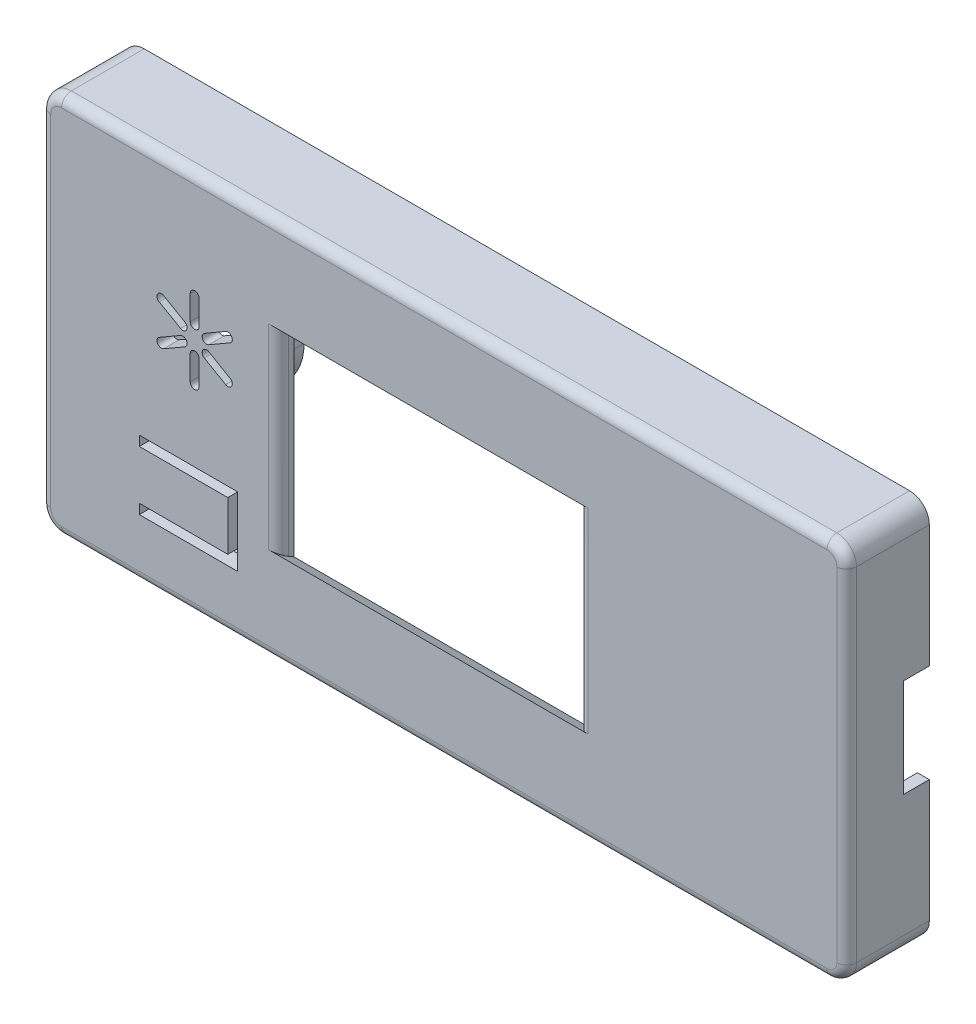
SolidWorks part; units mm, degrees
note: The reader was unsure of these and kept them because the rebuilt part matched: shared geometry of "Skizze1<10>", "Skizze1<23>", "Skizze1<24>", "Skizze1<36>", "Skizze1<38>".
ref_plane "Ebene vorne" through (0, 0, 0) normal (0, 0, 1) x (1, 0, 0)
ref_plane "Ebene oben" through (0, 0, 0) normal (0, 1, 0) x (1, 0, 0)
ref_plane "Ebene rechts" through (0, 0, 0) normal (1, 0, 0) x (0, 0, -1)
sketch "Skizze1" plane through (0, 0, 0) normal (0, 0, 1) x (1, 0, 0)
  line L0 (5.9, 21.251) -> (17.6, 21.251)
  line L1 (0, 33) -> (74, 33)
  line L2 (0, 33) -> (0, 0)
  line L3 (0, 0) -> (74, 0)
  line L4 (74, 33) -> (74, 0)
  line L5 (9, 8.7) -> (15, 8.7)
  line L6 (9, 8.7) -> (9, 2.9)
  line L7 (9, 2.9) -> (15, 2.9)
  line L8 (15, 8.7) -> (15, 2.9)
  line L9 (50, 30.1) -> (21, 30.1)
  line L10 (50, 30.1) -> (50, 2.9)
  line L11 (50, 2.9) -> (21, 2.9)
  line L12 (21, 30.1) -> (21, 2.9)
  line L13 (-2, 35) -> (76, 35)
  line L14 (-2, 35) -> (-2, -2)
  line L15 (-2, -2) -> (76, -2)
  line L16 (76, 35) -> (76, -2)
  line L17 (7.4, 21.251) -> (16.1, 21.251)
  line L18 (8.3728, 23.2004) -> (10.5378, 21.9504) construction
  line L19 (8.5978, 23.5901) -> (10.7628, 22.3401)
  line L20 (8.1478, 22.8107) -> (10.3128, 21.5607)
  line L21 (11.3009, 25.1491) -> (11.3009, 22.6491)
  line L22 (70, 21.5) -> (74, 21.5)
  line L23 (70, 21.5) -> (70, 11.5)
  line L24 (70, 11.5) -> (74, 11.5)
  line L25 (74, 21.5) -> (74, 11.5)
  line L26 (21, 30.1) -> (50, 30.1)
  line L27 (21, 30.1) -> (21, 26.1)
  line L28 (21, 26.1) -> (50, 26.1)
  line L29 (50, 30.1) -> (50, 26.1)
  line L30 (12.2009, 25.1491) -> (12.2009, 22.6491)
  line L31 (11.7509, 25.1491) -> (11.7509, 22.6491) construction
  line L32 (14.9026, 23.5875) -> (12.7376, 22.3375)
  line L33 (15.3526, 22.8081) -> (13.1876, 21.5581)
  line L34 (15.1276, 23.1978) -> (12.9626, 21.9478) construction
  line L35 (15.3511, 19.6876) -> (13.1861, 20.9376)
  line L36 (14.9011, 18.9082) -> (12.7361, 20.1582)
  line L37 (15.1261, 19.2979) -> (12.9611, 20.5479) construction
  line L38 (12.198, 17.3492) -> (12.198, 19.8492)
  line L39 (11.298, 17.3492) -> (11.298, 19.8492)
  line L40 (11.748, 17.3492) -> (11.748, 19.8492) construction
  line L41 (8.5963, 18.9108) -> (10.7613, 20.1608)
  line L42 (8.1463, 19.6902) -> (10.3113, 20.9402)
  line L43 (8.3713, 19.3005) -> (10.5363, 20.5505) construction
  arc A1 (5.9, 21.251) -> (17.6, 21.251) centre (11.75, 21.25) cw
  arc A2 (16.1, 21.251) -> (7.4, 21.251) centre (11.75, 21.25) ccw
  arc A3 (8.5978, 23.5901) -> (8.1478, 22.8107) centre (8.3728, 23.2004) ccw
  arc A4 (10.3128, 21.5607) -> (10.7628, 22.3401) centre (10.5378, 21.9504) ccw
  arc A5 (12.2009, 25.1491) -> (11.3009, 25.1491) centre (11.7509, 25.1491) ccw
  arc A6 (11.3009, 22.6491) -> (12.2009, 22.6491) centre (11.7509, 22.6491) ccw
  arc A7 (15.3526, 22.8081) -> (14.9026, 23.5875) centre (15.1276, 23.1978) ccw
  arc A8 (12.7376, 22.3375) -> (13.1876, 21.5581) centre (12.9626, 21.9478) ccw
  arc A9 (14.9011, 18.9082) -> (15.3511, 19.6876) centre (15.1261, 19.2979) ccw
  arc A10 (13.1861, 20.9376) -> (12.7361, 20.1582) centre (12.9611, 20.5479) ccw
  arc A11 (11.298, 17.3492) -> (12.198, 17.3492) centre (11.748, 17.3492) ccw
  arc A12 (12.198, 19.8492) -> (11.298, 19.8492) centre (11.748, 19.8492) ccw
  arc A13 (8.1463, 19.6902) -> (8.5963, 18.9108) centre (8.3713, 19.3005) ccw
  arc A14 (10.7613, 20.1608) -> (10.3113, 20.9402) centre (10.5363, 20.5505) ccw
  arc A15 (16.1, 21.251) -> (7.4, 21.251) centre (11.75, 21.252) cw
  arc A16 (5.9, 21.251) -> (17.6, 21.251) centre (11.75, 21.252) ccw
  point P24 (9.4553, 22.5754)
  point P40 (11.7509, 23.8991)
  point P47 (14.0451, 22.5728)
  point P54 (14.0436, 19.9229)
  point P61 (11.748, 18.5992)
  point P68 (9.4538, 19.9255)
  point P73 (11.7494, 21.2492)
  dimension "D3" = 4.35
  dimension "D16" = 0.45
  dimension "D1" = 33
  dimension "D5" = 11.75
  dimension "D6" = 6
  dimension "D7" = 5.8
  dimension "D8" = 8.7
  dimension "D9" = 15
  dimension "D10" = 74
  dimension "D11" = 2.9
  dimension "D13" = 50
  dimension "D14" = 53
  dimension "D12" = 2.9
  dimension "D15" = 2
  dimension "D17" = 2
  dimension "D18" = 2
  dimension "D19" = 2
  dimension "D20" = 11.7
  dimension "D4" = 2.5
  dimension "D21" = 2.65
  dimension "D22" = 4
  dimension "D23" = 4
  dimension "D24" = 10
  dimension "D25" = 11.5
  dimension "D26" = 4
  dimension "D27" = 11.75
  dimension "D28" = 30
  dimension "D29" = 0.001
  dimension "D30" = 0.001
  dimension "D32" = 0.001
  dimension "D31" = 6
extrude "Aufsatz-Linear austragen5" add sketch "Skizze1" along normal blind 1.5 contours L1 L4 L3 L2
extrude "Schnitt-Linear austragen1" cut sketch "Skizze1<10>" against normal through all and the other way through all
sketch "Skizze1<10>" plane through (0, 0, 0) normal (0, 0, 1) x (1, 0, 0) same geometry as "Skizze1"
extrude "Aufsatz-Linear austragen7" add sketch "Skizze1<23>" against normal blind 6.5 separate body contours L13 L16 L15 L14 | L1 L4 L3 L2
sketch "Skizze1<23>" plane through (0, 0, 0) normal (0, 0, 1) x (1, 0, 0) same geometry as "Skizze1"
extrude "Aufsatz-Linear austragen8" add sketch "Skizze1<24>" along normal blind 1.5 contours L16 L13 L14 L15 L1 L4 L3 L2
sketch "Skizze1<24>" plane through (0, 0, 0) normal (0, 0, 1) x (1, 0, 0) same geometry as "Skizze1"
sketch "Skizze3" plane through (0, 0, 1.5) normal (0, 0, 1) x (1, 0, 0)
  line L0 (13, 35) -> (13, -2)
  line L1 (-2, 35) -> (76, 35) construction
  line L2 (-2, -2) -> (76, -2) construction
  line L3 (76, 35) -> (76, -2) construction
  line L5 (13, 35) -> (76, 35)
  line L6 (13, 35) -> (13, -2)
  line L7 (13, -2) -> (76, -2)
  line L8 (76, -2) -> (76, 35)
  line L16 (76, 35) -> (76, -2)
  line L20 (76, 35) -> (-2, 35)
  line L24 (76, 35) -> (-2, 35)
  line L26 (-2, 35) -> (-2, -2)
  line L28 (-2, 35) -> (-2, -2)
  line L29 (-2, -2) -> (76, -2)
  line L30 (-2, -2) -> (76, -2)
  dimension "D1" = 63
  dimension "D2" = 0
sketch "Skizze13" plane through (0, 0, 0) normal (0, 0, -1) x (-1, 0, 0)
  line L0 (-74, 33) -> (-74, 0) construction
  line L1 (-50.75, 33) -> (-74, 33)
  line L2 (-50.75, 33) -> (-50.75, 0)
  line L3 (-50.75, 0) -> (-74, 0)
  line L4 (-74, 33) -> (-74, 0)
  line L5 (0, 33) -> (-74, 33) construction
  line L6 (0, 0) -> (-74, 0) construction
  line L7 (-50, 30.1) -> (-50, 2.9) construction
  dimension "D1" = 0
  dimension "D2" = 0
  dimension "D3" = 0.75
extrude "Schnitt-Linear austragen10" cut sketch "Skizze13" against normal offset from surface (0.5 mm away) 1 up to face at (35.5, 16.5, 1.5)
sketch "Skizze14" plane through (0, 0, 0) normal (0, 0, -1) x (-1, 0, 0)
  line L0 (-21, 30.1) -> (-21, 2.9) construction
  line L1 (-50, 30.1) -> (-21, 30.1)
  line L2 (-50, 30.1) -> (-50, 31.6)
  line L3 (-50, 31.6) -> (-21, 31.6)
  line L4 (-21, 30.1) -> (-21, 31.6)
  line L5 (-50, 2.9) -> (-21, 2.9)
  line L6 (-50, 2.9) -> (-50, 1.4)
  line L7 (-50, 1.4) -> (-21, 1.4)
  line L8 (-21, 2.9) -> (-21, 1.4)
  dimension "D1" = 1.5
  dimension "D2" = 1.5
  dimension "D3" = 0
  dimension "D4" = 0
extrude "Schnitt-Linear austragen11" cut sketch "Skizze14" against normal blind 8
sketch "Skizze15" plane through (0, 0, 0) normal (1, 0, 0) x (0, 0, -1)
  line L0 (6.5, 33) -> (6.5, 0) construction
  line L1 (6.5, 25) -> (4.5, 25)
  line L2 (6.5, 25) -> (6.5, 8)
  line L3 (6.5, 8) -> (4.5, 8)
  line L4 (4.5, 25) -> (4.5, 8)
  line L5 (6.5, 33) -> (0, 33) construction
  line L6 (6.5, 0) -> (0, 0) construction
  dimension "D1" = 8
  dimension "D2" = 8
sketch "Skizze16" plane through (0, 0, -6.5) normal (0, 0, -1) x (-1, 0, 0)
  line L0 (-50.75, 33) -> (-74, 33) construction
  line L1 (-74.85, 33.85) -> (0.85, 33.85)
  line L2 (-74.85, 33.85) -> (-74.85, -0.85)
  line L3 (-74.85, -0.85) -> (0.85, -0.85)
  line L4 (0.85, 33.85) -> (0.85, -0.85)
  line L5 (-74, 33) -> (-74, 0) construction
  line L6 (0, 0) -> (-74, 0) construction
  line L7 (0, 33) -> (0, 0) construction
  dimension "D1" = 0.85
  dimension "D2" = 0.85
  dimension "D3" = 0.85
  dimension "D4" = 0.85
extrude "Schnitt-Linear austragen12" cut sketch "Skizze16" against normal blind 2.5
fillet "Verrundung7" radius 2 2 edges at (-2, 35, -2.5) (-2, -2, -2.5)
ref_plane "Ebene1" through (37, 0, 0) normal (-1, 0, 0) x (0, 0, 1)
scale "Skalieren1" bodies to scale 126 scale about centroid uniform scaling yes scale factor 1.05
fillet "Verrundung10" radius 1 6 edges at (-3.8783, 16.5, 1.6221) (38.1217, 35.925, 1.6221) (38.1217, -2.925, 1.6221) (-3.2632, -2.3099, 1.6221) (-3.2632, 35.3099, 1.6221) (78.0217, 16.5, 1.6221)
sketch "Skizze21" plane through (0, 32.355, 0) normal (0, -1, 0) x (1, 0, 0)
  line L0 (20.2717, 0.0471) -> (50.7217, 0.0471) construction
  line L1 (20.2717, 1.6221) -> (51.2197, 1.6221)
  line L2 (20.2717, 1.6221) -> (20.2717, 0.0471)
  line L3 (20.2717, 0.0471) -> (51.2197, 0.0471)
  line L4 (51.2197, 1.6221) -> (51.2197, 0.0471)
extrude "Aufsatz-Linear austragen14" add sketch "Skizze21" along normal blind 6
chamfer "Fase1" distance 1 angle 60 1 edges at (35.4967, 26.355, 0.0471)
ref_plane "Ebene2" through (0, 16.5, 0) normal (0, 1, 0) x (1, 0, 0)
mirror "Spiegeln2" about plane through (0, 16.5, 0) normal (0, 1, 0) of "Aufsatz-Linear austragen14", "Fase1"
fillet "Verrundung11" radius 1 2 edges at (50.7217, 16.5, 1.6221) (20.2717, 16.5, 1.6221)
fillet "Verrundung12" radius 2 4 edges at (78.0217, -2.925, -3.0779) (78.0217, 35.925, -3.0779) (77.7288, -2.6321, 1.3293) (77.7288, 35.6321, 1.3293)
sketch "Skizze23" plane through (76.8142, 0, 0) normal (-1, 0, 0) x (0, 0, 1)
  line L0 (-4.1529, 34.7175) -> (-4.1529, -1.7175) construction
  line L1 (-4.1529, 21.5) -> (-6.7779, 21.5)
  line L2 (-4.1529, 21.5) -> (-4.1529, 11.5)
  line L3 (-4.1529, 11.5) -> (-6.7779, 11.5)
  line L4 (-6.7779, 21.5) -> (-6.7779, 11.5)
  line L5 (-6.7779, 34.7175) -> (-6.7779, -1.7175) construction
  line L6 (4.07, 16.5) -> (-4.07, 16.5) construction
  point P8 (-5.4654, 11.5)
  dimension "D1" = 10
extrude "Schnitt-Linear austragen13" cut sketch "Skizze23" against normal up to surface (1.2075 mm away)
sketch "Skizze25" plane through (0, -1.7175, 0) normal (0, 1, 0) x (1, 0, 0)
  line L0 (12, 5.2779) -> (62, 5.2779) construction
  line L1 (12, 5.7779) -> (62, 5.7779)
  line L2 (12, 4.7779) -> (62, 4.7779)
  line L3 (37, 4.07) -> (37, -4.07) construction
  line L5 (76.8142, 6.7779) -> (-2.6708, 6.7779) construction
  arc A0 (12, 5.7779) -> (12, 4.7779) centre (12, 5.2779) ccw
  arc A1 (62, 4.7779) -> (62, 5.7779) centre (62, 5.2779) ccw
  point P2 (37, 5.2779)
  dimension "D1" = 0.5
  dimension "D2" = 50
  dimension "D3" = 25
  dimension "D4" = 1.5
sketch "Skizze26" plane through (0, 34.7175, 0) normal (0, -1, 0) x (1, 0, 0)
  line L0 (16, -5.3779) -> (37, -5.3779)
  line L1 (37, -5.3779) -> (37, -4.7779)
  line L2 (37, -4.7779) -> (16.6, -4.7779)
  line L3 (37, 4.07) -> (37, -4.07) construction
  line L4 (-2.6708, -6.7779) -> (76.8142, -6.7779) construction
  arc A0 (16, -5.3779) -> (16.6, -4.7779) centre (16.6, -5.3779) cw
  dimension "D4" = 0.6
  dimension "D1" = 0
  dimension "D2" = 2
  dimension "D3" = 0.6
  dimension "D5" = 21
revolve "Schnitt-Rotation1" cut sketch "Skizze26" angle 360 about L0
mirror "Spiegeln3" about plane through (37, 0, 0) normal (-1, 0, 0) of "Schnitt-Rotation1"
mirror "Spiegeln4" about plane through (0, 16.5, 0) normal (0, 1, 0) of "Schnitt-Rotation1", "Spiegeln3"
sketch "Skizze27" plane through (0, 0, 1.6221) normal (0, 0, 1) x (1, 0, 0)
  line L0 (6.1217, 10.075) -> (16.1217, 10.075)
  line L1 (16.1217, 10.075) -> (16.1217, 3.075)
  line L2 (16.1217, 3.075) -> (6.1217, 3.075)
  line L3 (6.1217, 3.075) -> (6.1217, 4.075)
  line L4 (6.1217, 4.075) -> (15.1217, 4.075)
  line L5 (15.1217, 4.075) -> (15.1217, 9.075)
  line L6 (15.1217, 9.075) -> (6.1217, 9.075)
  line L7 (6.1217, 9.075) -> (6.1217, 10.075)
  line L8 (-2.8783, 33.825) -> (-2.8783, -0.825) construction
  line L9 (-1.7783, -1.925) -> (76.0217, -1.925) construction
  dimension "D1" = 19
  dimension "D2" = 10
  dimension "D4" = 1
  dimension "D5" = 1
  dimension "D6" = 12
  dimension "D7" = 7
  dimension "D8" = 10
extrude "Schnitt-Linear austragen14" cut sketch "Skizze27" against normal up to surface (1.575 mm away) up to face at (35.4967, 16.5, 0.0471)
sketch "Skizze29" plane through (0, 0, 0.0471) normal (0, 0, -1) x (-1, 0, 0)
  line L1 (-15.1217, 9.075) -> (-6.1217, 9.075)
  line L2 (-15.1217, 9.075) -> (-15.1217, 4.075)
  line L3 (-15.1217, 4.075) -> (-6.1217, 4.075)
  line L4 (-6.1217, 9.075) -> (-6.1217, 4.075)
extrude "Aufsatz-Linear austragen16" add sketch "Skizze29" along normal blind 1 separate body
extrude "Schnitt-Linear austragen16" cut sketch "Skizze1<36>" along normal up to surface (1.6221 mm away) contours L30 A6 L21 A5 | L33 A8 L32 A7 | L35 A10 L36 A9 | L38 A12 L39 A11 | L41 A14 L42 A13 | L20 A4 L19 A3 up to face at (10.8717, 6.575, 1.6221)
sketch "Skizze1<36>" plane through (0, 0, 0) normal (0, 0, 1) x (1, 0, 0) same geometry as "Skizze1"
extrude "Aufsatz-Linear austragen17" add sketch "Skizze1<38>" against normal offset from surface 0.5 and the other way up to next contours A2 L0 A1 | L0 A16 A15 A9 A11 A13
sketch "Skizze1<38>" plane through (0, 0, 0) normal (0, 0, 1) x (1, 0, 0) same geometry as "Skizze1"
equation "\"D12@Skizze1\"=\"D11@Skizze1\""
equation "\"D17@Skizze1\"=\"D15@Skizze1\""
equation "\"D18@Skizze1\"=\"D15@Skizze1\""
equation "\"D19@Skizze1\"=\"D15@Skizze1\""
equation "\"D2@Skizze15\"=\"D1@Skizze15\""
equation "\"D3@Skizze16\"=\"D1@Skizze16\""
equation "\"D4@Skizze16\"=\"D1@Skizze16\""
equation "\"D2@Skizze16\"=\"D1@Skizze16\""
equation "\"D2@Skizze23\"= \"D1@Skizze23\" / 2"
equation "\"D3@Skizze25\"=\"D2@Skizze25\"/2"
equation "\"D4@Skizze27\"=\"D3@Skizze27\""
equation "\"D5@Skizze27\"=\"D3@Skizze27\""
equation "\"D8@Skizze27\"=\"D2@Skizze27\""
